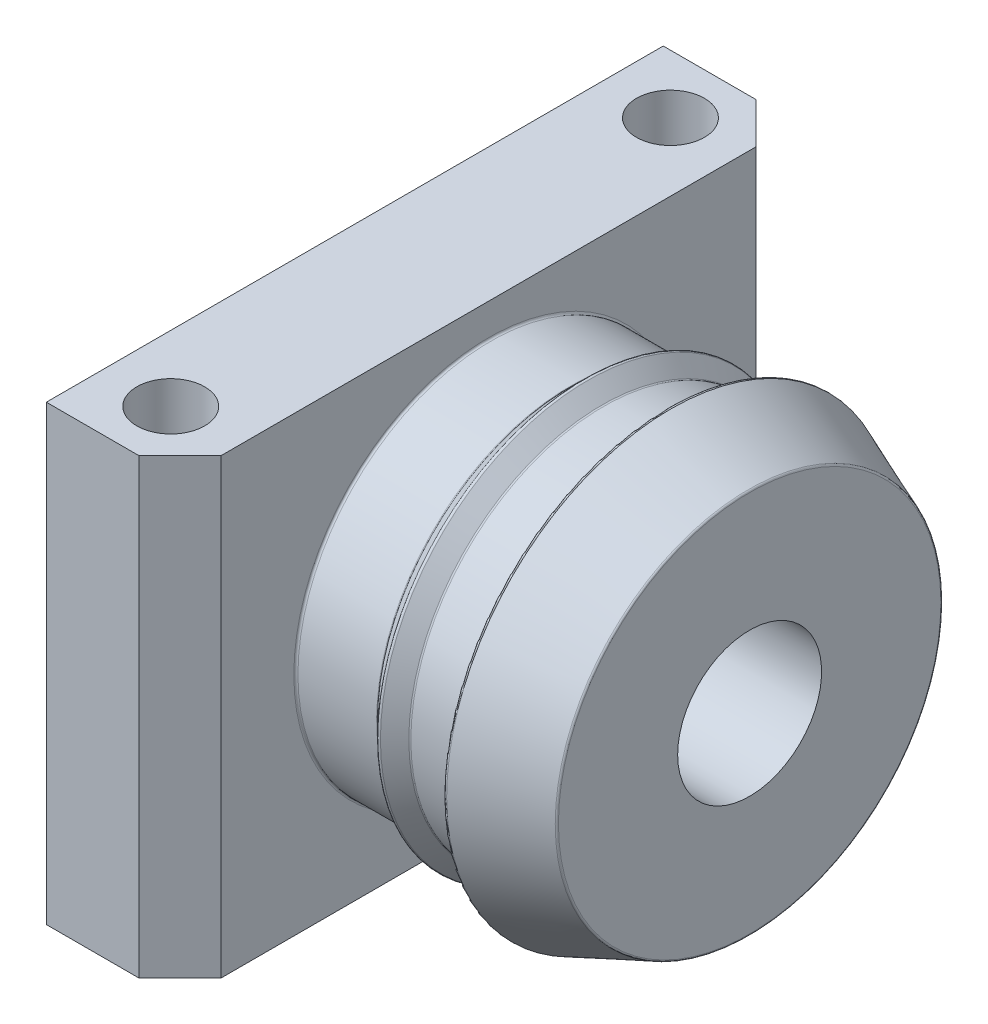
SolidWorks part; units mm, degrees
note: The reader was unsure of these and kept them because the rebuilt part matched: shared geometry of "Sketch2<3>", "Sketch2<4>", "Sketch2<5>", "Sketch2<6>".
ref_plane "Front Plane" through (0, 0, 0) normal (0, 0, 1) x (1, 0, 0)
ref_plane "Top Plane" through (0, 0, 0) normal (0, 1, 0) x (1, 0, 0)
ref_plane "Right Plane" through (0, 0, 0) normal (1, 0, 0) x (0, 0, -1)
sketch "Sketch1" plane through (0, 0, 0) normal (0, 1, 0) x (1, 0, 0)
  line L0 (0, 0) -> (-12.7, 0)
  line L1 (0, 0) -> (0, 9.365)
  line L2 (0, 9.365) -> (-3.97, 10.955)
  line L3 (-3.97, 10.955) -> (-3.97, 9.365)
  line L4 (0, 9.365) -> (-19.3321, 9.365) construction
  line L5 (-3.97, 9.365) -> (-7.15, 9.365)
  line L6 (-7.15, 9.365) -> (-7.94, 10.155)
  line L7 (-7.94, 10.155) -> (-8.73, 9.365)
  line L8 (-8.73, 9.365) -> (-12.7, 9.365)
  line L9 (-12.7, 9.365) -> (-12.7, 0)
  dimension "D1" = 12.7
  dimension "D2" = 9.365
  dimension "D3" = 1.59
  dimension "D4" = 3.97
  dimension "D5" = 7.94
  dimension "D6" = 0.79
revolve "Revolve1" add sketch "Sketch1" angle 360 about L0
sketch "Sketch2" plane through (-12.7, 0, 0) normal (-1, 0, 0) x (0, 0, 1)
  line L0 (0.92, 2.735) -> (0.92, -1.615)
  line L1 (-8.59, 6.425) -> (8.59, 6.425) construction
  line L2 (-8.59, 6.425) -> (-8.59, -6.425) construction
  line L3 (-8.59, -6.425) -> (8.59, -6.425) construction
  line L4 (8.59, 6.425) -> (8.59, -6.425) construction
  line L5 (-8.59, 6.425) -> (8.59, -6.425) construction
  line L6 (-8.59, -6.425) -> (8.59, 6.425) construction
  line L7 (0.92, -1.615) -> (-1.54, -1.615)
  line L8 (-1.54, -1.615) -> (-1.54, 2.735)
  line L9 (-1.54, 2.735) -> (0.92, 2.735)
  line L10 (0, 6.425) -> (0, -6.425) construction
  line L11 (15, 11) -> (-15, 11)
  line L12 (15, 11) -> (15, -11)
  line L13 (15, -11) -> (-15, -11)
  line L14 (-15, 11) -> (-15, -11)
  line L15 (15, 11) -> (-15, -11) construction
  line L16 (15, -11) -> (-15, 11) construction
  line L18 (-8.59, -6.425) -> (8.59, -6.425)
  line L19 (-8.59, -6.425) -> (-8.59, -4.625)
  line L20 (-8.59, -4.625) -> (8.59, -4.625)
  line L21 (8.59, -6.425) -> (8.59, -4.625)
  line L22 (-8.59, -6.425) -> (8.59, -4.625) construction
  line L23 (-8.59, -4.625) -> (8.59, -6.425) construction
  line L28 (-9.29, 6.625) -> (9.29, 6.625)
  line L29 (-9.29, 6.625) -> (-9.29, -7.425)
  line L30 (-9.29, -7.425) -> (9.29, -7.425)
  line L31 (9.29, 6.625) -> (9.29, -7.425)
  line L32 (-9.29, 6.625) -> (9.29, -7.425) construction
  line L33 (-9.29, -7.425) -> (9.29, 6.625) construction
  circle A0 centre (-6.19, 3.935) radius 0.9
  circle A1 centre (6.19, 3.935) radius 0.9
  circle A2 centre (0, 0) radius 3.5
  point P0 (0, 0)
  point P8 (0, 0)
  point P25 (0, -5.525)
  point P35 (0, -0.4)
  circle M5 centre (0, 0) radius 9.365
  dimension "D9" = 1.8
  dimension "D10" = 2.49
  dimension "D11" = 2.4
  dimension "D12" = 7
  dimension "D1" = 12.85
  dimension "D2" = 17.18
  dimension "D3" = 7.67
  dimension "D4" = 3.69
  dimension "D5" = 2.46
  dimension "D6" = 4.35
  dimension "D7" = 22
  dimension "D8" = 30
  dimension "D13" = 1.8
  dimension "D14" = 0.7
  dimension "D15" = 0.7
  dimension "D16" = 0.2
  dimension "D17" = 1
extrude "Boss-Extrude1" add sketch "Sketch2" along normal blind 1.5
extrude "Boss-Extrude2" add sketch "Sketch2<3>" along normal offset from surface (2 mm away) 0.5 contours L20 L18 M5 | L18 L21 L20 M5 | L20 L19 L18 M5 up to face at (-14.2, 0, 0) offset beyond the face yes
sketch "Sketch2<3>" plane through (-12.7, 0, 0) normal (-1, 0, 0) x (0, 0, 1) same geometry as "Sketch2"
extrude "Boss-Extrude3" add sketch "Sketch2<4>" along normal offset from surface (5 mm away) 3.5 contours A1 | A0 up to face at (-14.2, -5.525, 0) offset beyond the face yes
sketch "Sketch2<4>" plane through (-12.7, 0, 0) normal (-1, 0, 0) x (0, 0, 1) same geometry as "Sketch2"
extrude "Cut-Extrude1" cut sketch "Sketch2<5>" against normal through all contours A2 L8 L9 L0 L7 | L9 L8 L7 L0
sketch "Sketch2<5>" plane through (-12.7, 0, 0) normal (-1, 0, 0) x (0, 0, 1) same geometry as "Sketch2"
extrude "Boss-Extrude4" add sketch "Sketch2<6>" along normal offset from surface (6.5 mm away) 5 contours L11 L14 L13 L12 L28 L31 L30 L29 M5 | L30 M5 | L31 M5 | L29 M5 | L28 M5
sketch "Sketch2<6>" plane through (-12.7, 0, 0) normal (-1, 0, 0) x (0, 0, 1) same geometry as "Sketch2"
fillet "Fillet1" radius 0.1 7 edges at (-12.7, 0, 9.365) (-8.73, 0, -9.365) (-7.15, 0, -9.365) (-7.94, 0, -10.155) (-3.97, 0, -9.365) (-3.97, 0, -10.955) (0, 0, -9.365)
fillet "Fillet4" radius 0.2 2 edges at (-17.7, 3.935, -5.29) (-17.7, 3.935, 7.09)
fillet "Fillet5" radius 0.2 4 edges at (-14.7, -5.525, -8.59) (-14.7, -6.425, 0) (-14.7, -5.525, 8.59) (-14.7, -4.625, 0)
ref_plane "Plane1" through (0, 3.5, 0) normal (0, -1, 0) x (-1, 0, 0)
sketch "Sketch4" plane through (0, 3.5, 0) normal (0, -1, 0) x (-1, 0, 0)
  line L0 (16, 9.3) -> (16, 15) construction
  line L2 (19.2, 15) -> (12.7, 15) construction
  line L3 (12.7, -15) -> (12.7, 15) construction
  circle A0 centre (16, 12.15) radius 1.65
  point P10 (16, 12.15)
  dimension "D1" = 3.3
  dimension "D2" = 3.3
  dimension "D3" = 5.7
extrude "Cut-Extrude2" cut sketch "Sketch4" against normal through all and the other way through all
ref_plane "Plane2" through (0, 0, 0) normal (0, 0, -1) x (-1, 0, 0)
mirror "Mirror1" about plane through (0, 0, 0) normal (0, 0, -1) of "Cut-Extrude2"
sketch "Sketch5" plane through (0, 0, 0) normal (0, 0, -1) x (-1, 0, 0)
  line L0 (17.9, -11) -> (17.9, -9.8342)
  line L1 (19.2, -11) -> (12.7, -11) construction
  line L2 (17.9, -9.8342) -> (15.4, -11)
  line L3 (15.4, -11) -> (17.9, -11)
  line L4 (19.2, 11) -> (19.2, -11) construction
  line L5 (14.35, -11) -> (17.65, -11) construction
  dimension "D1" = 1.3
  dimension "D2" = 2.5
  dimension "D3" = 65
extrude "Cut-Extrude3" cut sketch "Sketch5" against normal blind 7 and the other way blind 7
sketch "Sketch6" plane through (-19.2, 0, 0) normal (-1, 0, 0) x (0, 0, 1)
  line L0 (-9.29, 6.625) -> (-9.29, -7.425) construction
  line L1 (-9.29, 8.625) -> (9.29, 8.625)
  line L2 (-11.29, 6.625) -> (-11.29, -6.425)
  line L3 (-9.29, -8.425) -> (9.29, -8.425)
  line L4 (11.29, 6.625) -> (11.29, -6.425)
  line L5 (-11.29, 8.625) -> (11.29, -8.425) construction
  line L6 (-11.29, -8.425) -> (11.29, 8.625) construction
  line L7 (9.29, 6.625) -> (-9.29, 6.625) construction
  line L8 (9.29, 6.625) -> (9.29, -7.425) construction
  line L9 (9.29, -7.425) -> (-9.29, -7.425) construction
  arc A0 (9.29, -8.425) -> (11.29, -6.425) centre (9.29, -6.425) ccw
  arc A1 (9.29, 8.625) -> (11.29, 6.625) centre (9.29, 6.625) cw
  arc A2 (-9.29, 8.625) -> (-11.29, 6.625) centre (-9.29, 6.625) ccw
  arc A3 (-11.29, -6.425) -> (-9.29, -8.425) centre (-9.29, -6.425) ccw
  point P4 (0, 0.1)
  point P13 (0, 0)
  point P14 (0, 0)
  point P27 (0, 0)
  point P28 (0, 0)
  dimension "D5" = 2
  dimension "D1" = 2
  dimension "D2" = 2
  dimension "D3" = 2
  dimension "D4" = 1
sweep "Cut-Sweep1" cut path "Sketch6" circular profile diameter 1.778 parameters "D3"=1.778
fillet "Fillet6" radius 0.2 2 edges at (-14.2, 3.935, -5.29) (-14.2, 3.935, 7.09)
chamfer "Chamfer1" distance 2 angle 45 2 edges at (-12.7, 0, 15) (-12.7, 0, -15)
equation "\"WallThick\"= 1.2'thickness of wall for printer"
equation "\"D3@Sketch4\"=\"WallThick\"*2+\"dHole\""
equation "\"dHole\"= 3.3'diameter of screw hole"
